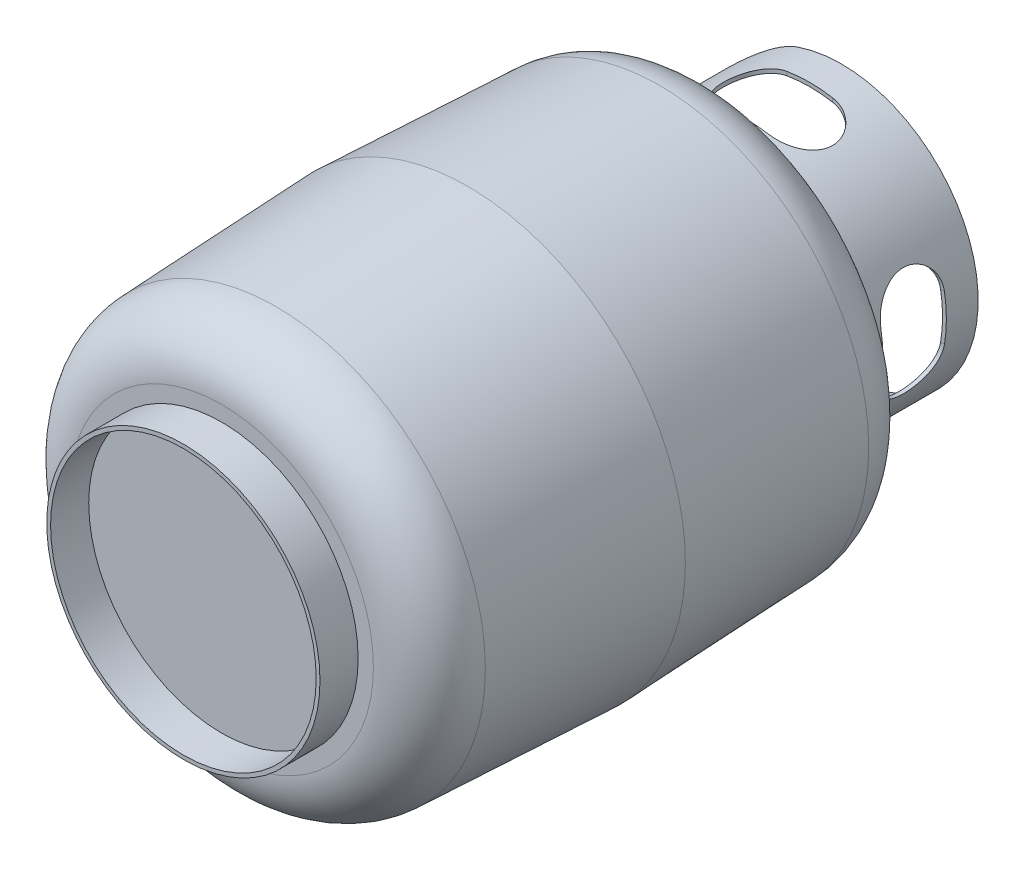
SolidWorks part; units mm, degrees
material "1060 Alloy"
ref_plane "Front Plane" through (0, 0, 0) normal (0, 0, 1) x (1, 0, 0)
ref_plane "Top Plane" through (0, 0, 0) normal (0, 1, 0) x (1, 0, 0)
ref_plane "Right Plane" through (0, 0, 0) normal (1, 0, 0) x (0, 0, -1)
sketch "Sketch1" plane through (0, 0, 0) normal (0, 1, 0) x (1, 0, 0)
  line L0 (0, 0) -> (119.4219, 0)
  line L1 (164.379, 43.0371) -> (170.9593, 193.75)
  line L2 (170.9593, 193.75) -> (164.379, 344.4629)
  line L3 (119.4219, 387.5) -> (25, 387.5)
  line L4 (25, 387.5) -> (25, 407.5)
  line L5 (25, 407.5) -> (0, 407.5)
  line L6 (0, 0) -> (0, 491.9606) construction
  line L7 (0, 4) -> (119.4219, 4)
  line L8 (160.3828, 43.2116) -> (166.9555, 193.75)
  line L9 (166.9555, 193.75) -> (160.3828, 344.2884)
  line L10 (119.4219, 383.5) -> (21, 383.5)
  line L11 (21, 383.5) -> (21, 403.5)
  line L12 (21, 403.5) -> (0, 403.5)
  line L13 (0, 407.5) -> (0, 403.5)
  line L14 (0, 4) -> (0, 0)
  arc A0 (164.379, 344.4629) -> (119.4219, 387.5) centre (119.4219, 342.5) ccw
  arc A1 (119.4219, 0) -> (164.379, 43.0371) centre (119.4219, 45) ccw
  arc A2 (119.4219, 4) -> (160.3828, 43.2116) centre (119.4219, 45) ccw
  arc A3 (160.3828, 344.2884) -> (119.4219, 383.5) centre (119.4219, 342.5) ccw
  point P10 (162.5, 387.5)
  point P14 (162.5, 0)
  dimension "D8" = 45
  dimension "D9" = 45
  dimension "D1" = 162.5
  dimension "D2" = 92.5
  dimension "D3" = 162.5
  dimension "D4" = 387.5
  dimension "D5" = 25
  dimension "D6" = 20
  dimension "D7" = 92.5
  dimension "D10" = 4
revolve "Revolve1" add sketch "Sketch1" angle 360 about L6
sketch "Sketch2" plane through (0, 0, -407.5) normal (0, 0, -1) x (-1, 0, 0)
  circle A0 centre (0, 0) radius 21
extrude "Cut-Extrude1" cut sketch "Sketch2" along normal blind 89 and the other way blind 140
sketch "Sketch3" plane through (0, 0, 0) normal (0, 0, 1) x (1, 0, 0)
  circle A0 centre (0, 0) radius 107.4219
  circle A1 centre (0, 0) radius 119.4219 construction
  circle A2 centre (0, 0) radius 104.4219
  dimension "D1" = 12
  dimension "D2" = 3
extrude "Boss-Extrude1" add sketch "Sketch3" along normal blind 30
sketch "Sketch4" plane through (0, 0, -387.5) normal (0, 0, -1) x (-1, 0, 0)
  line L0 (0, 0) -> (119.4219, 0) construction
  line L1 (0, 0) -> (61.6147, 87.9948) construction
  line L2 (0, 0) -> (61.6147, -87.9948) construction
  line L3 (61.6147, 87.9948) -> (59.8939, 85.5374)
  line L4 (59.8939, -85.5374) -> (61.6147, -87.9948)
  arc A0 (61.6147, 87.9948) -> (61.6147, -87.9948) centre (0, 0) ccw
  circle A1 centre (0, 0) radius 119.4219 construction
  arc A3 (59.8939, 85.5374) -> (59.8939, -85.5374) centre (0, 0) ccw
  dimension "D1" = 12
  dimension "D2" = 55
  dimension "D3" = 55
  dimension "D4" = 3
extrude "Boss-Extrude2" add sketch "Sketch4" along normal blind 100
fillet "Fillet3" radius 30 2 edges at (-60.7543, -86.7661, -487.5) (-60.7543, 86.7661, -487.5)
sketch "Sketch5" plane through (0, 0, 0) normal (0, 1, 0) x (1, 0, 0)
  line L0 (0, 0) -> (0, 437.5) construction
  line L1 (119.4219, 387.5) -> (-119.4219, 387.5) construction
  line L2 (119.4219, 387.5) -> (-119.4219, 387.5)
  line L3 (18, 437.5) -> (-18, 437.5) construction
  line L5 (18, 412.5) -> (-18, 412.5)
  line L6 (18, 462.5) -> (-18, 462.5)
  arc A0 (18, 412.5) -> (18, 462.5) centre (18, 437.5) ccw
  arc A1 (-18, 462.5) -> (-18, 412.5) centre (-18, 437.5) ccw
  point P9 (0, 437.5)
  dimension "D2" = 25
  dimension "D1" = 50
  dimension "D3" = 36
extrude "Cut-Extrude2" cut sketch "Sketch5" against normal mid plane 310 contours A1 L5 A0 L6
sketch "Sketch6" plane through (0, 0, 0) normal (1, 0, 0) x (0, 0, -1)
  line L0 (0, 0) -> (437.5, 0) construction
  line L1 (387.5, -107.4219) -> (387.5, 107.4219) construction
  line L2 (437.5, 18) -> (437.5, -18) construction
  line L4 (462.5, 18) -> (462.5, -18)
  line L5 (412.5, 18) -> (412.5, -18)
  arc A0 (462.5, 18) -> (412.5, 18) centre (437.5, 18) ccw
  arc A1 (412.5, -18) -> (462.5, -18) centre (437.5, -18) ccw
  point P9 (437.5, 0)
  dimension "D2" = 25
  dimension "D1" = 50
  dimension "D3" = 36
extrude "Cut-Extrude3" cut sketch "Sketch6" along normal blind 310
equation "\"a\"= 325mm"
equation "\"b\"= 387.5mm"
